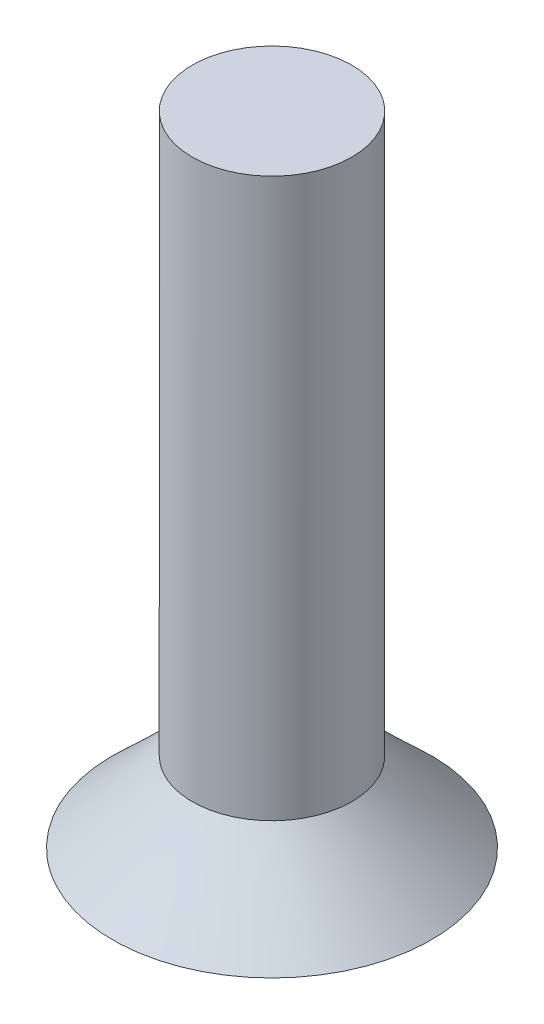
SolidWorks part; units mm, degrees
ref_plane "Ön Düzlem" through (0, 0, 0) normal (0, 0, 1) x (1, 0, 0)
ref_plane "Üst Düzlem" through (0, 0, 0) normal (0, 1, 0) x (1, 0, 0)
ref_plane "Sağ Düzlem" through (0, 0, 0) normal (1, 0, 0) x (0, 0, -1)
sketch "Sketch1" plane through (0, 0, 0) normal (0, 1, 0) x (1, 0, 0)
  circle A0 centre (0, 0) radius 3
  dimension "D1" = 6
ref_plane "Plane1" through (0, 1.5, 0) normal (0, 1, 0) x (1, 0, 0)
sketch "Sketch2" plane through (0, 1.5, 0) normal (0, 1, 0) x (1, 0, 0)
  circle A0 centre (0, 0) radius 1.5
  dimension "D1" = 3
loft "Loft1" add profiles "Sketch1", "Sketch2" connector at (2.28, 0, -1.9498) connector at (0.6944, 1.5, -1.3296)
sketch "Sketch9" plane through (0, 1.5, 0) normal (0, 1, 0) x (1, 0, 0)
  circle A0 centre (0, 0) radius 1.5
extrude "Boss-Extrude1" add sketch "Sketch9" along normal blind 10.5
sketch "Sketch10" plane through (0, 0, 0) normal (0, -1, 0) x (-1, 0, 0)
  line L1 (-1.4434, 0) -> (-0.7217, -1.25)
  line L2 (-0.7217, -1.25) -> (0.7217, -1.25)
  line L3 (0.7217, -1.25) -> (1.4434, 0)
  line L4 (1.4434, 0) -> (0.7217, 1.25)
  line L5 (0.7217, 1.25) -> (-0.7217, 1.25)
  line L6 (-0.7217, 1.25) -> (-1.4434, 0)
  circle A0 centre (0, 0) radius 1.25 construction
  dimension "D1" = 2.5
extrude "Cut-Extrude1" cut sketch "Sketch10" against normal blind 1
